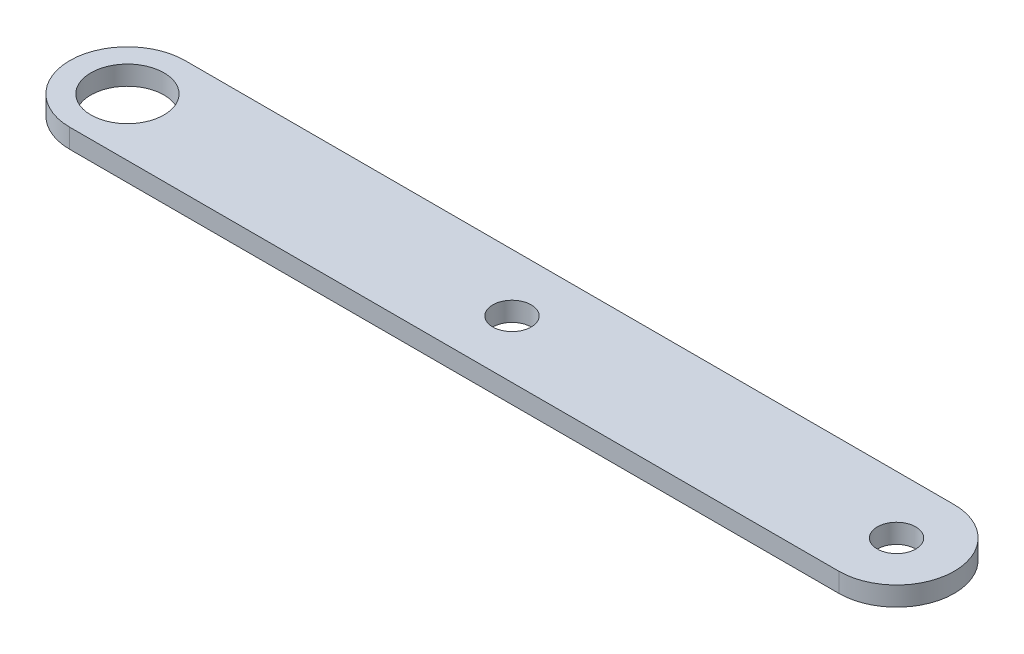
SolidWorks part; units mm, degrees
ref_plane "前视基准面" through (0, 0, 0) normal (0, 0, 1) x (1, 0, 0)
ref_plane "上视基准面" through (0, 0, 0) normal (0, 1, 0) x (1, 0, 0)
ref_plane "右视基准面" through (0, 0, 0) normal (1, 0, 0) x (0, 0, -1)
other "Configuration Table"
sketch "草图1" plane through (0, 0, 0) normal (0, 1, 0) x (1, 0, 0)
  line L0 (0, 0) -> (200, 0) construction
  line L1 (0, 15) -> (200, 15)
  line L2 (0, -15) -> (200, -15)
  arc A0 (0, 15) -> (0, -15) centre (0, 0) ccw
  arc A1 (200, -15) -> (200, 15) centre (200, 0) ccw
  circle A2 centre (200, 0) radius 5
  circle A3 centre (100, 0) radius 5
  circle A4 centre (0, 0) radius 9.5
  point P3 (100, 0)
  dimension "D2" = 15
  dimension "D3" = 10
  dimension "D4" = 19
  dimension "D5" = 10
  dimension "D1" = 200
extrude "凸台-拉伸1" add sketch "草图1" along normal blind 5
